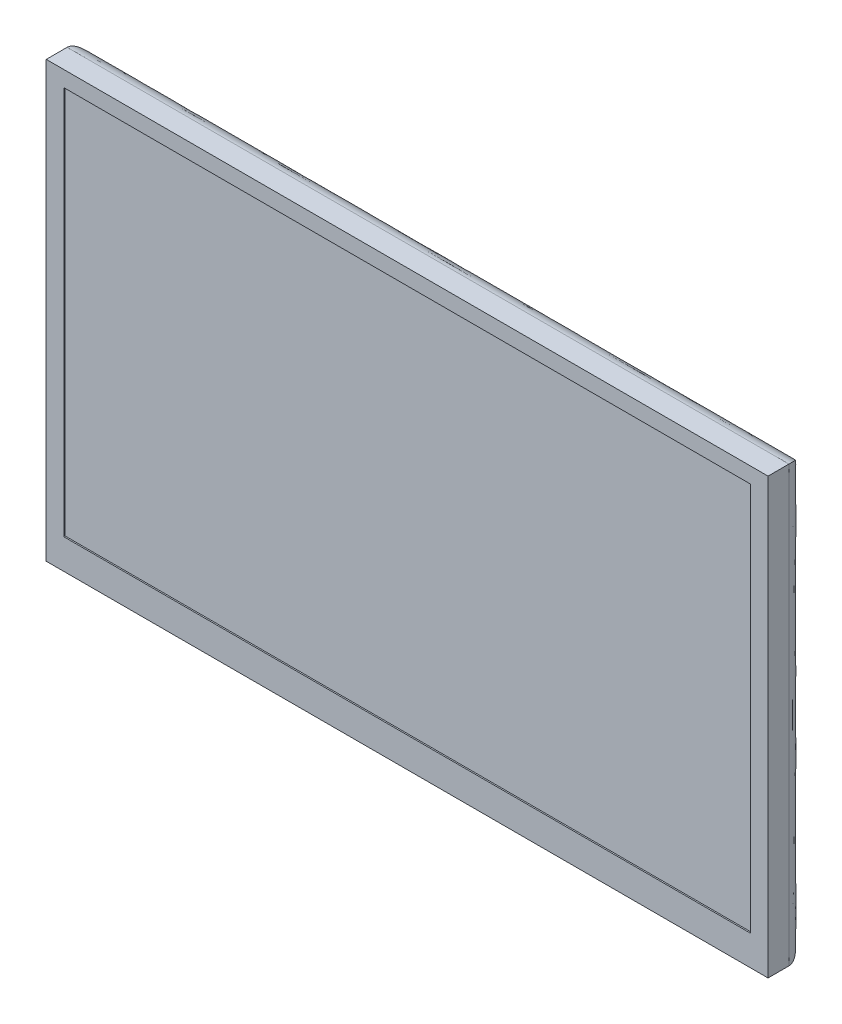
SolidWorks part; units mm, degrees
ref_plane "Спереди" through (0, 0, 0) normal (0, 0, 1) x (1, 0, 0)
ref_plane "Сверху" through (0, 0, 0) normal (0, 1, 0) x (1, 0, 0)
ref_plane "Справа" through (0, 0, 0) normal (1, 0, 0) x (0, 0, -1)
sketch "Эскиз1" plane through (0, 0, 0) normal (0, 0, 1) x (1, 0, 0)
  line L1 (-56.6364, 26.4202) -> (496.3636, 26.4202)
  line L2 (-56.6364, 26.4202) -> (-56.6364, -306.5798)
  line L3 (-56.6364, -306.5798) -> (496.3636, -306.5798)
  line L4 (496.3636, 26.4202) -> (496.3636, -306.5798)
  dimension "D1" = 553
  dimension "D2" = 333
extrude "Бобышка-Вытянуть1" add sketch "Эскиз1" against normal blind 56
fillet "Скругление1" radius 150 4 edges at (219.8636, -306.5798, -56) (-56.6364, -140.0798, -56) (219.8636, 26.4202, -56) (496.3636, -140.0798, -56) second distance 40 first distance on face at (219.8636, -140.0798, -56)
sketch "Эскиз2" plane through (0, 0, 0) normal (0, 0, 1) x (1, 0, 0)
  line L0 (496.3636, 26.4202) -> (-56.6364, 26.4202) construction
  line L1 (-43.1364, 14.4202) -> (482.8636, 14.4202)
  line L2 (-43.1364, 14.4202) -> (-43.1364, -283.5798)
  line L3 (-43.1364, -283.5798) -> (482.8636, -283.5798)
  line L4 (482.8636, 14.4202) -> (482.8636, -283.5798)
  line L5 (219.8636, -306.5798) -> (219.8636, 36.5669) construction
  line L6 (-56.6364, -306.5798) -> (496.3636, -306.5798) construction
  point P10 (219.8636, 14.4202)
  dimension "D1" = 526
  dimension "D2" = 298
  dimension "D3" = 12
extrude "Вырез-Вытянуть1" cut sketch "Эскиз2" against normal blind 1
sketch "Эскиз3" plane through (0, -306.5798, 0) normal (0, -1, 0) x (1, 0, 0)
  line L1 (371.3636, -4.1987) -> (461.3636, -4.1987)
  line L2 (371.3636, -4.1987) -> (371.3636, -12.0837)
  line L3 (371.3636, -12.0837) -> (461.3636, -12.0837)
  line L4 (461.3636, -4.1987) -> (461.3636, -12.0837)
  line L5 (496.3636, -16) -> (496.3636, 0) construction
  dimension "D1" = 90
  dimension "D2" = 35
extrude "Бобышка-Вытянуть2" add sketch "Эскиз3" along normal blind 3
sketch3d "Трехмерный эскиз1"
  line L0 (219.8636, -306.5798, 0) -> (219.8636, 26.4202, 0) construction
  line L1 (-56.6364, -306.5798, 0) -> (496.3636, -306.5798, 0) construction
  line L2 (496.3636, 26.4202, 0) -> (-56.6364, 26.4202, 0) construction
ref_plane "Плоскость1" through (219.8636, 0, 0) normal (-1, 0, 0) x (0, 0, 1)
